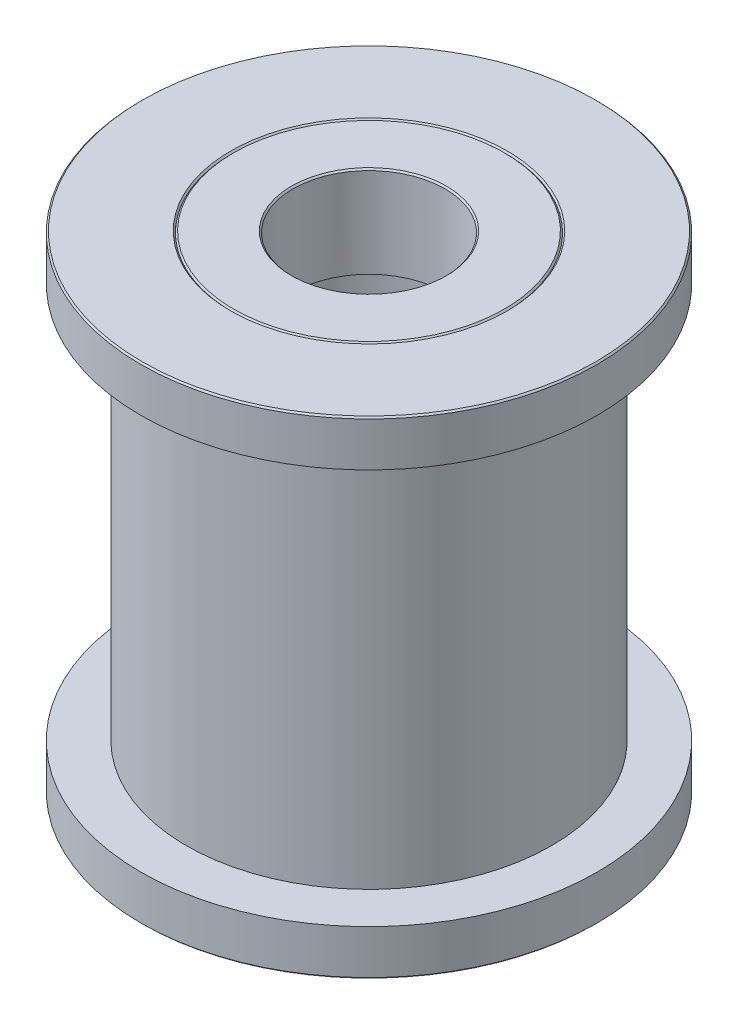
SolidWorks part; units mm, degrees
ref_plane "Front Plane" through (0, 0, 0) normal (0, 0, 1) x (1, 0, 0)
ref_plane "Top Plane" through (0, 0, 0) normal (0, 1, 0) x (1, 0, 0)
ref_plane "Right Plane" through (0, 0, 0) normal (1, 0, 0) x (0, 0, -1)
sketch "Sketch1" plane through (0, 0, 0) normal (0, 0, 1) x (1, 0, 0)
  line L0 (0, -12.8882) -> (0, 12.8882) construction
  line L1 (6, 5.9242) -> (7.5, 5.9242)
  line L5 (7.5, 7.4242) -> (7.5, 5.9242)
  line L9 (4.5, -8.5758) -> (4.5, -5.5758)
  line L16 (4.5, 7.4242) -> (7.5, 7.4242)
  line L17 (6, -7.0758) -> (6, 5.9242)
  line L18 (6, -7.0758) -> (7.5, -7.0758)
  line L19 (3.5, -5.5758) -> (3.5, 4.4242)
  line L22 (3.5, 4.4242) -> (4.5, 4.4242)
  line L23 (4.5, 7.4242) -> (4.5, 4.4242)
  line L24 (7.5, -7.0758) -> (7.5, -8.5758)
  line L25 (3.5, -5.5758) -> (4.5, -5.5758)
  line L26 (4.5, -8.5758) -> (7.5, -8.5758)
  line L28 (4.5, 4.4242) -> (2.5, 4.4242)
  line L29 (4.5, 4.4242) -> (4.5, 7.4242)
  line L30 (4.5, 7.4242) -> (2.5, 7.4242)
  line L31 (2.5, 4.4242) -> (2.5, 7.4242)
  line L32 (4.5, -5.5758) -> (2.5, -5.5758)
  line L33 (4.5, -5.5758) -> (4.5, -8.5758)
  line L34 (4.5, -8.5758) -> (2.5, -8.5758)
  line L35 (2.5, -5.5758) -> (2.5, -8.5758)
  point P4 (0, 0)
  dimension "D1" = 16
  dimension "D2" = 1.5
  dimension "D3" = 3
  dimension "D4" = 1.5
  dimension "D5" = 3.5
  dimension "D6" = 4.5
  dimension "D7" = 6
  dimension "D8" = 7.5
  dimension "D9" = 3
  dimension "D10" = 1
  dimension "D11" = 2
  dimension "D12" = 2
revolve "Revolve1" add sketch "Sketch1" angle 360 about L0 region at (5.1006, -0.5758, 0)
chamfer "Chamfer1" distance 0.05 angle 45 4 edges at (4.5, -8.5758, 0) (4.5, 7.4242, 0) (7.5, 7.4242, 0) (7.5, -8.5758, 0)
revolve "Revolve2" add sketch "Sketch1<3>" angle 360 about L0 region at (3.5, 5.9242, 0) region at (3.5, -7.0758, 0)
sketch "Sketch1<3>" plane through (0, 0, 0) normal (0, 0, 1) x (1, 0, 0) same geometry as "Sketch1"
chamfer "Chamfer2" distance 0.05 angle 45 2 edges at (4.5, -8.5758, 0) (2.5, -8.5758, 0)
chamfer "Chamfer3" distance 0.05 angle 45 2 edges at (4.5, 7.4242, 0) (2.5, 7.4242, 0)
